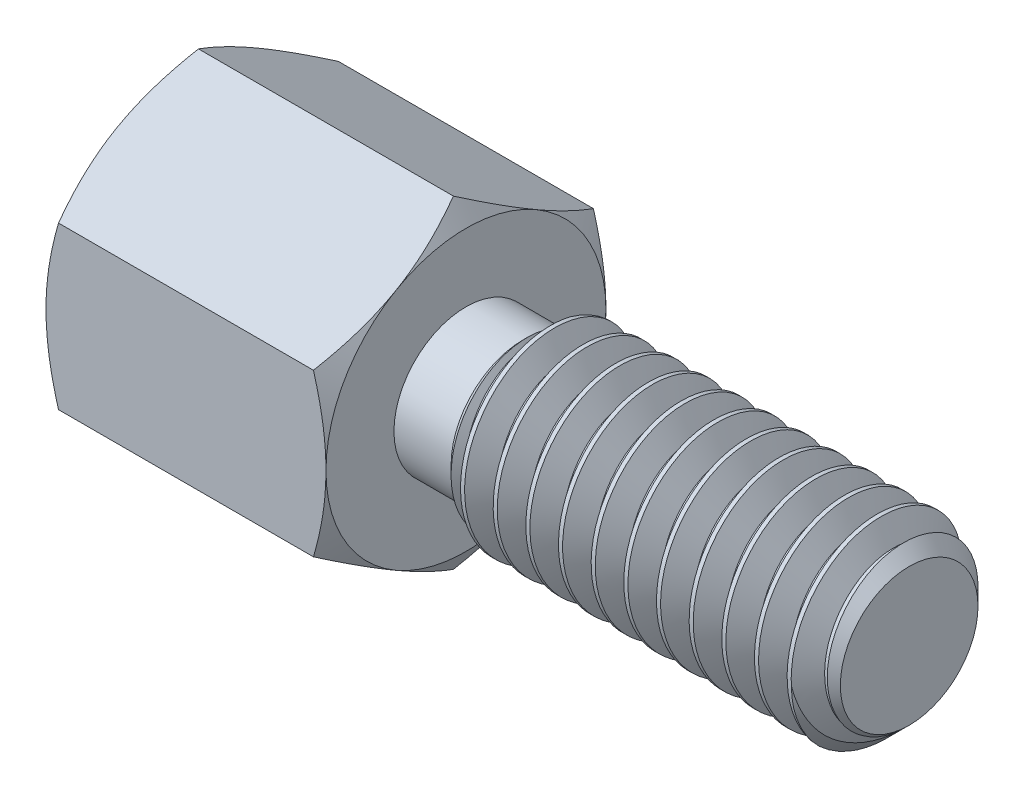
SolidWorks part; units mm, degrees
ref_plane "Front Plane" through (0, 0, 0) normal (0, 0, 1) x (1, 0, 0)
ref_plane "Top Plane" through (0, 0, 0) normal (0, 1, 0) x (1, 0, 0)
ref_plane "Right Plane" through (0, 0, 0) normal (1, 0, 0) x (0, 0, -1)
sketch "Sketch1" plane through (0, 0, 0) normal (0, 0, 1) x (1, 0, 0)
  line L0 (-7.75, 0) -> (7.75, 0) construction
  line L1 (7.75, 2) -> (7.75, -2) construction
  line L2 (-7.75, 3) -> (-7.75, -3) construction
  line L3 (-5.65, 2) -> (-5.65, -2) construction
  line L4 (-5.65, -2) -> (-7.75, -2) construction
  line L5 (-5.65, 2) -> (-7.75, 2) construction
  line L6 (-7.75, 3) -> (-1.75, 3) construction
  line L7 (-7.75, -3) -> (-1.75, -3) construction
  point P2 (-1.75, 0)
  point P8 (-5.65, 0)
  point P13 (4.6, -2)
  dimension "D1" = 3.15
  dimension "Hex" = 6
  dimension "Male Thread" = 4
  dimension "A" = 6
  dimension "B" = 9.5
  dimension "C" = 2.1
  dimension "Female Thread" = 4
ref_plane "Plane1" through (7.75, 0, 0) normal (1, 0, 0) x (0, 0, -1)
sketch "Sketch2" plane through (7.75, 0, 0) normal (1, 0, 0) x (0, 0, -1)
  circle A0 centre (0, 0) radius 2
extrude "Extrude1" add sketch "Sketch2" against normal up to vertex (9.5 mm away) up to point (-1.75, 0, 0)
sketch "Sketch3" plane through (7.75, 0, 0) normal (1, 0, 0) x (0, 0, -1)
  circle A1 centre (0, 0) radius 2
  circle A2 centre (0, 0) radius 2
  dimension "D1" = 0
curve "Helix/Spiral1" pitch 0.7 height 10.2 turns 14.5714 parameters "Male Pitch"=0.7
chamfer "Chamfer1" distance 0.525 angle 45 1 edges at (7.75, 0, -2)
sketch "Sketch4" plane through (0, 0, 0) normal (0, 0, 1) x (1, 0, 0)
  line L0 (7.75, 2) -> (8.3625, 2)
  line L1 (8.3625, 2) -> (8.1, 1.5453)
  line L2 (8.1, 1.5453) -> (8.0125, 1.5453)
  line L3 (8.0125, 1.5453) -> (7.75, 2)
  line L4 (8.0563, 1.5453) -> (8.0563, 2) construction
  line L5 (7.8813, 1.7727) -> (8.2313, 1.7727) construction
  dimension "D1" = 0.0875
  dimension "D2" = 0.35
  dimension "D3" = 60
sweep "Cut-Sweep1" cut profiles "Sketch4" path "Helix/Spiral1"
sketch "Sketch16" plane through (0, 0, 0) normal (0, 0, 1) x (1, 0, 0)
  line L0 (-1.75, 1.5428) -> (-0.525, 1.5428)
  line L1 (-0.525, 1.5428) -> (-0.0678, 2)
  line L2 (-0.0678, 2) -> (-1.75, 2)
  line L3 (-1.75, 2) -> (-1.75, 1.5428)
  line L4 (7.75, 2) -> (8.3625, 2) construction
  line L5 (0, 0) -> (7.75, 0) construction
  line L6 (7.75, -1.475) -> (7.75, 1.475) construction
  dimension "D1" = 1.225
  dimension "D2" = 45
  dimension "D3" = 0.0025
revolve "Cut-Revolve1" cut sketch "Sketch16" angle 360 about L5
ref_plane "Plane2" through (-1.75, 0, 0) normal (1, 0, 0) x (0, 0, -1)
sketch "Sketch7" plane through (-1.75, 0, 0) normal (1, 0, 0) x (0, 0, -1)
  line L1 (0, 3.4641) -> (-3, 1.7321)
  line L2 (-3, 1.7321) -> (-3, -1.7321)
  line L3 (-3, -1.7321) -> (0, -3.4641)
  line L4 (0, -3.4641) -> (3, -1.7321)
  line L5 (3, -1.7321) -> (3, 1.7321)
  line L6 (3, 1.7321) -> (0, 3.4641)
  circle A0 centre (0, 0) radius 3 construction
extrude "Extrude4" add sketch "Sketch7" against normal up to vertex (6 mm away) up to point (-7.75, 0, 0)
sketch "Sketch17" plane through (0, 0, 0) normal (0, 0, 1) x (1, 0, 0)
  line L0 (-7.75, -3.4641) -> (-1.75, -3.4641) construction
  line L1 (-7.75, 3.4641) -> (-1.75, 3.4641) construction
  line L2 (-7.75, -3.4641) -> (-1.75, -3.4641)
  line L3 (-7.75, 3.4641) -> (-1.75, 3.4641)
sketch "Sketch8" plane through (-7.75, 0, 0) normal (-1, 0, 0) x (0, 0, 1)
  circle A0 centre (0, 0) radius 3 construction
  circle A1 centre (0, 0) radius 3
extrude "Extrude5" cut sketch "Sketch8" against normal through all draft 60 flip side to cut
sketch "Sketch9" plane through (-1.75, 0, 0) normal (1, 0, 0) x (0, 0, -1)
  circle A0 centre (0, 0) radius 3 construction
  circle A1 centre (0, 0) radius 3
extrude "Extrude6" cut sketch "Sketch9" against normal through all draft 60 flip side to cut
sketch "Sketch10" plane through (-7.75, 0, 0) normal (-1, 0, 0) x (0, 0, 1)
  line L0 (0, 0) -> (-1.4142, 1.4142) construction
  line L1 (0, 0) -> (-2, 0) construction
  circle A0 centre (0, 0) radius 2
  dimension "D1" = 45
extrude "Extrude7" cut sketch "Sketch10" against normal up to vertex (2.1 mm away) up to point (-5.65, 0, 0)
sketch "Sketch11" plane through (-7.75, 0, 0) normal (-1, 0, 0) x (0, 0, 1)
  circle A0 centre (0, 0) radius 2 construction
  circle A1 centre (0, 0) radius 2
curve "Helix/Spiral2" pitch 0.7 height 2.1 radius 2 centre (-7.75, 0, 0) axis (1, 0, 0) start towards (0, 1, 0) parameters "Female Pitch"=0.7
sketch "Sketch12" plane through (0, 0, 0) normal (0, 0, 1) x (1, 0, 0)
  line L0 (-8.3625, 2) -> (-8.1, 1.5453)
  line L1 (-8.1, 1.5453) -> (-8.0125, 1.5453)
  line L2 (-8.0125, 1.5453) -> (-7.75, 2)
  line L3 (-8.3625, 2) -> (-7.75, 2)
  line L4 (-8.0562, 1.5453) -> (-8.0562, 2) construction
  line L5 (-7.75, 3) -> (-7.75, -3) construction
  line L6 (-8.2312, 1.7727) -> (-7.8812, 1.7727) construction
  dimension "D1" = 60
  dimension "D2" = 0.0875
  dimension "D3" = 0.35
sweep "Sweep3" add profiles "Sketch12" path "Helix/Spiral2"
sketch "Sketch13" plane through (-7.75, 0, 0) normal (-1, 0, 0) x (0, 0, 1)
  circle A2 centre (0, 0) radius 2.0508
  circle A3 centre (0, 0) radius 2.0508
  dimension "D1" = 0.0508
extrude "Extrude8" cut sketch "Sketch13" along normal through all and the other way through all draft 45
equation "\"D3@Helix/Spiral1\" = \"B@Sketch1\"+\"Male Pitch@Helix/Spiral1\"*1"
equation "\"D1@Chamfer1\" = \"Male Pitch@Helix/Spiral1\"*.750"
equation "\"D1@Sketch4\" = \"Male Pitch@Helix/Spiral1\"*.125"
equation "\"D2@Sketch4\" = \"Male Pitch@Helix/Spiral1\"*.5"
equation "\"D2@Sketch12\" = \"Male Pitch@Helix/Spiral1\"*.125"
equation "\"D3@Sketch12\" = \"Male Pitch@Helix/Spiral1\"*.5"
equation "\"D3@Helix/Spiral2\" = \"C@Sketch1\""
equation "\"Female Thread@Sketch1\" = \"Male Thread@Sketch1\""
equation "\"Female Pitch@Helix/Spiral2\" = \"Male Pitch@Helix/Spiral1\""
equation "\"D1@Sketch16\" = \"Male Pitch@Helix/Spiral1\"*1.75"
equation "\"D1@Sketch1\" = \"Male Pitch@Helix/Spiral1\"*4.5"
